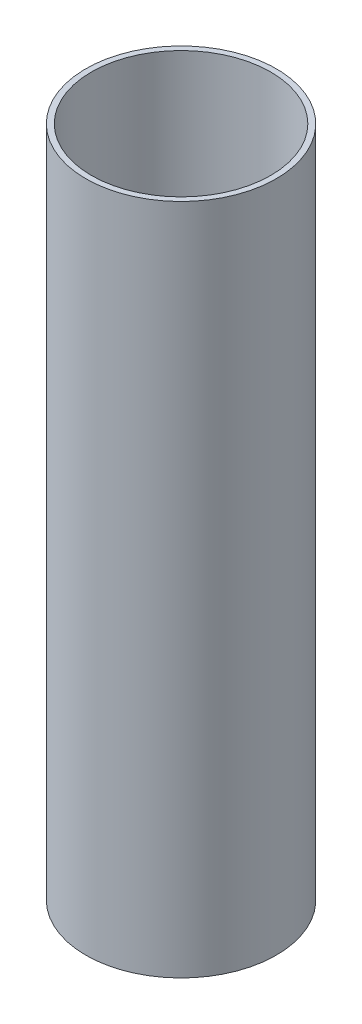
SolidWorks part; units mm, degrees
ref_plane "Front Plane" through (0, 0, 0) normal (0, 0, 1) x (1, 0, 0)
ref_plane "Top Plane" through (0, 0, 0) normal (0, 1, 0) x (1, 0, 0)
ref_plane "Right Plane" through (0, 0, 0) normal (1, 0, 0) x (0, 0, -1)
sketch "Sketch1" plane through (0, 0, 0) normal (0, 1, 0) x (1, 0, 0)
  circle A0 centre (0, 0) radius 101.6
  circle A1 centre (0, 0) radius 107.95
extrude "Boss-Extrude1" add sketch "Sketch1" along normal blind 762 contours A1 A0 region at (-104.8967, 0, 0)
